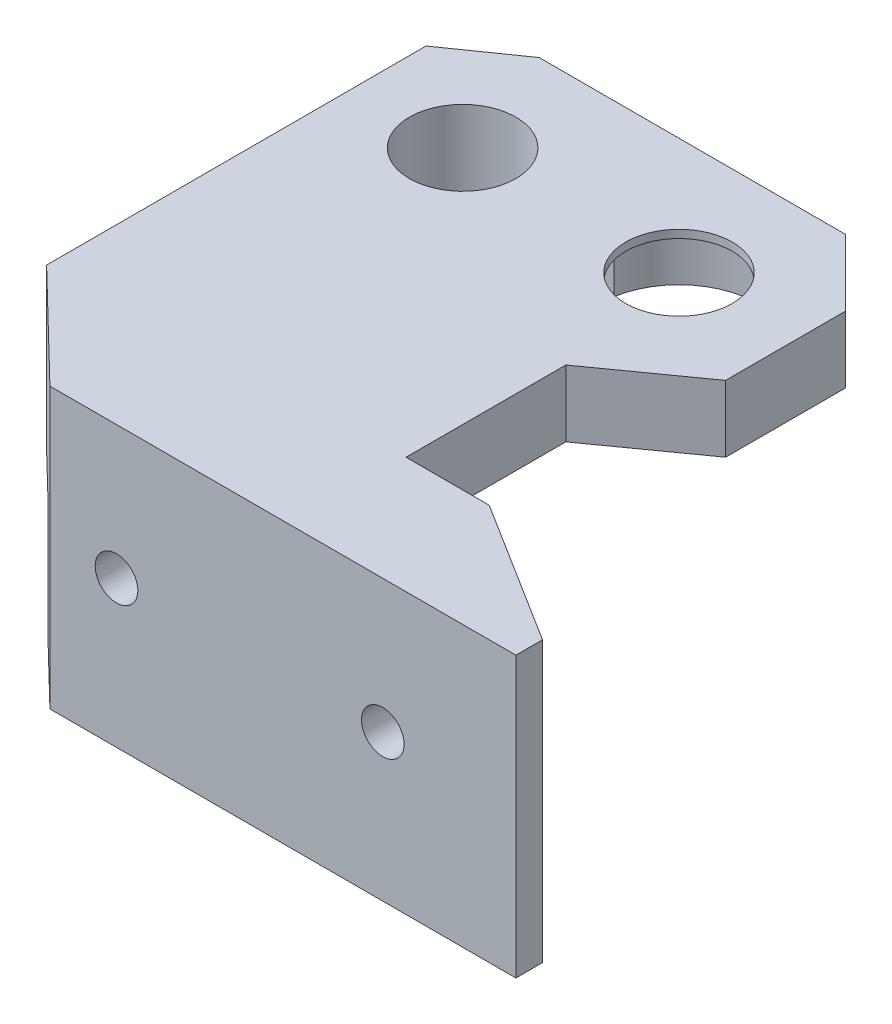
SolidWorks part; units mm, degrees
ref_plane "Front Plane" through (0, 0, 0) normal (0, 0, 1) x (1, 0, 0)
ref_plane "Top Plane" through (0, 0, 0) normal (0, 1, 0) x (1, 0, 0)
ref_plane "Right Plane" through (0, 0, 0) normal (1, 0, 0) x (0, 0, -1)
sketch "Sketch1" plane through (0, 0, 0) normal (0, 1, 0) x (1, 0, 0)
  line L0 (0, 0) -> (16.25, 0) construction
  line L5 (-3.75, 8.75) -> (19.25, 8.75)
  line L6 (19.25, 8.75) -> (24.25, 5.25)
  line L7 (24.25, 5.25) -> (24.25, -23.25)
  line L8 (24.25, -23.25) -> (16.25, -31)
  line L9 (16.25, -31) -> (-18.75, -31)
  line L10 (-18.75, -31) -> (-18.75, -29)
  line L11 (-18.75, -29) -> (-8, -22.25)
  line L12 (-8, -22.25) -> (-1.75, -22.25)
  line L13 (-1.75, -22.25) -> (-1.75, -10.25)
  line L14 (-1.75, -10.25) -> (-8.75, -5.25)
  line L15 (-8.75, -5.25) -> (-8.75, 3.75)
  line L16 (-8.75, 3.75) -> (-3.75, 8.75)
  line L17 (16.25, 0) -> (24.25, 0) construction
  circle A0 centre (0, 0) radius 4
  circle A1 centre (16.25, 0) radius 4
  point P0 (0, 0)
  dimension "D2" = 8
  dimension "D3" = 8
  dimension "D1" = 16.25
  dimension "D4" = 23
  dimension "D5" = 5
  dimension "D6" = 3.5
  dimension "D7" = 28.5
  dimension "D8" = 8
  dimension "D9" = 8.75
  dimension "D10" = 5
  dimension "D11" = 5
  dimension "D12" = 7
  dimension "D13" = 5
  dimension "D14" = 9
  dimension "D15" = 8
  dimension "D16" = 7.75
  dimension "D17" = 35
  dimension "D18" = 6.25
  dimension "D19" = 6.75
  dimension "D20" = 2
extrude "Boss-Extrude1" add sketch "Sketch1" along normal blind 5
sketch "Sketch2" plane through (0, 0, 0) normal (0, -1, 0) x (1, 0, 0)
  line L0 (24.25, 23.25) -> (24.25, -5.25)
  line L1 (24.25, -5.25) -> (20.75, -5.25)
  line L2 (20.75, -5.25) -> (20.75, 22.25)
  line L3 (20.75, 22.25) -> (-8, 22.25)
  line L4 (-8, 22.25) -> (-14.3704, 26.25)
  line L5 (-8, 22.25) -> (-18.75, 29) construction
  line L6 (-14.3704, 26.25) -> (21.1532, 26.25)
  line L7 (16.25, 31) -> (24.25, 23.25) construction
  line L8 (21.1532, 26.25) -> (24.25, 23.25)
  dimension "D1" = 3.5
  dimension "D2" = 4
extrude "Boss-Extrude2" add sketch "Sketch2" along normal blind 7
sketch "Sketch3" plane through (0, 0, 0) normal (0, -1, 0) x (1, 0, 0)
  line L5 (-14.3704, 26.25) -> (21.1532, 26.25)
  line L6 (21.1532, 26.25) -> (16.25, 31)
  line L7 (16.25, 31) -> (-18.75, 31)
  line L8 (-18.75, 31) -> (-18.75, 29)
  line L9 (-18.75, 29) -> (-14.3704, 26.25)
  line L10 (-14.3704, 26.25) -> (21.1532, 26.25)
  line L11 (21.1532, 26.25) -> (16.25, 31)
  line L12 (16.25, 31) -> (-18.75, 31)
  line L13 (-18.75, 31) -> (-18.75, 29)
  line L14 (-18.75, 29) -> (-14.3704, 26.25)
  dimension "D1" = 0
extrude "Boss-Extrude3" add sketch "Sketch3" along normal blind 16
sketch "Sketch6" plane through (0, 0, 0) normal (0, -1, 0) x (1, 0, 0)
  circle A0 centre (16.25, 0) radius 7
  circle A1 centre (16.25, 0) radius 4
  dimension "D1" = 14
extrude "Boss-Extrude4" add sketch "Sketch6" along normal blind 2.5
sketch "Sketch4" plane through (0, 0, 0) normal (0, -1, 0) x (1, 0, 0)
  line L0 (0, 0) -> (12.25, 0) construction
  line L1 (5.8838, -1) -> (12.377, -1)
  line L2 (5.8838, 1) -> (12.377, 1)
  line L3 (0, -1) -> (16.25, -1) construction
  line L4 (0, 1) -> (16.25, 1) construction
  line L5 (0, 0) -> (16.25, 0) construction
  arc A0 (5.8838, 1) -> (5.8838, -1) centre (0, 0) ccw
  arc A2 (12.377, 1) -> (12.377, -1) centre (16.25, 0) ccw
  dimension "D1" = 1
  dimension "D2" = 1
extrude "Cut-Extrude1" cut sketch "Sketch4" against normal blind 4.4
sketch "Sketch7" plane through (0, 4.4, 0) normal (0, -1, 0) x (1, 0, 0)
  line L2 (5.8838, -1) -> (12.377, -1)
  line L3 (12.377, 1) -> (5.8838, 1)
  line L4 (5.8838, -1) -> (12.377, -1)
  line L5 (12.377, 1) -> (5.8838, 1)
  arc A2 (5.8838, 1) -> (5.8838, -1) centre (0, 0) ccw
  arc A3 (12.377, 1) -> (12.377, -1) centre (16.25, 0) ccw
  arc A4 (5.8838, 1) -> (5.8838, -1) centre (0, 0) ccw
  arc A5 (12.377, 1) -> (12.377, -1) centre (16.25, 0) ccw
  dimension "D1" = 0
extrude "Cut-Extrude2" cut sketch "Sketch7" along normal through all
sketch "Sketch8" plane through (0, 0, 31) normal (0, 0, 1) x (1, 0, 0)
  line L0 (11.25, -5) -> (-8.75, -5) construction
  line L1 (-18.75, 5) -> (16.25, 5) construction
  line L2 (-18.75, 5) -> (-18.75, -16) construction
  circle A0 centre (11.25, -5) radius 1.6
  circle A1 centre (-8.75, -5) radius 1.6
  dimension "D1" = 3.2
  dimension "D2" = 3.2
  dimension "D3" = 20
  dimension "D4" = 10
  dimension "D5" = 10
extrude "Cut-Extrude3" cut sketch "Sketch8" against normal through all
sketch "Sketch9" plane through (0, 0, 22.25) normal (0, 0, -1) x (-1, 0, 0)
  circle A0 centre (-11.25, -5) radius 3
  circle A1 centre (8.75, -5) radius 3
  dimension "D1" = 6
  dimension "D2" = 6
extrude "Cut-Extrude4" cut sketch "Sketch9" against normal blind 4
mirror "Mirror1" about plane through (-18.75, 5, 31) normal (1, 0, 0) of "Boss-Extrude2", "Boss-Extrude4", "Cut-Extrude2", "Cut-Extrude3", "Cut-Extrude1", "Boss-Extrude3", "Boss-Extrude1", "Cut-Extrude4"
sketch "Sketch10" plane through (0, 5, 0) normal (0, 1, 0) x (1, 0, 0)
  line L0 (19.25, 8.75) -> (-3.75, 8.75) construction
  line L1 (30.4721, -31) -> (-18.75, -31)
  line L2 (30.4721, -31) -> (30.4721, 8.75)
  line L3 (30.4721, 8.75) -> (-18.75, 8.75)
  line L4 (-18.75, -31) -> (-18.75, 8.75)
  line L5 (30.4721, -31) -> (-18.75, 8.75) construction
  line L6 (30.4721, 8.75) -> (-18.75, -31) construction
  line L7 (16.25, -31) -> (-53.75, -31) construction
  point P0 (5.861, -11.125)
  point P8 (-18.75, -31)
extrude "Cut-Extrude5" cut sketch "Sketch10" against normal through all
